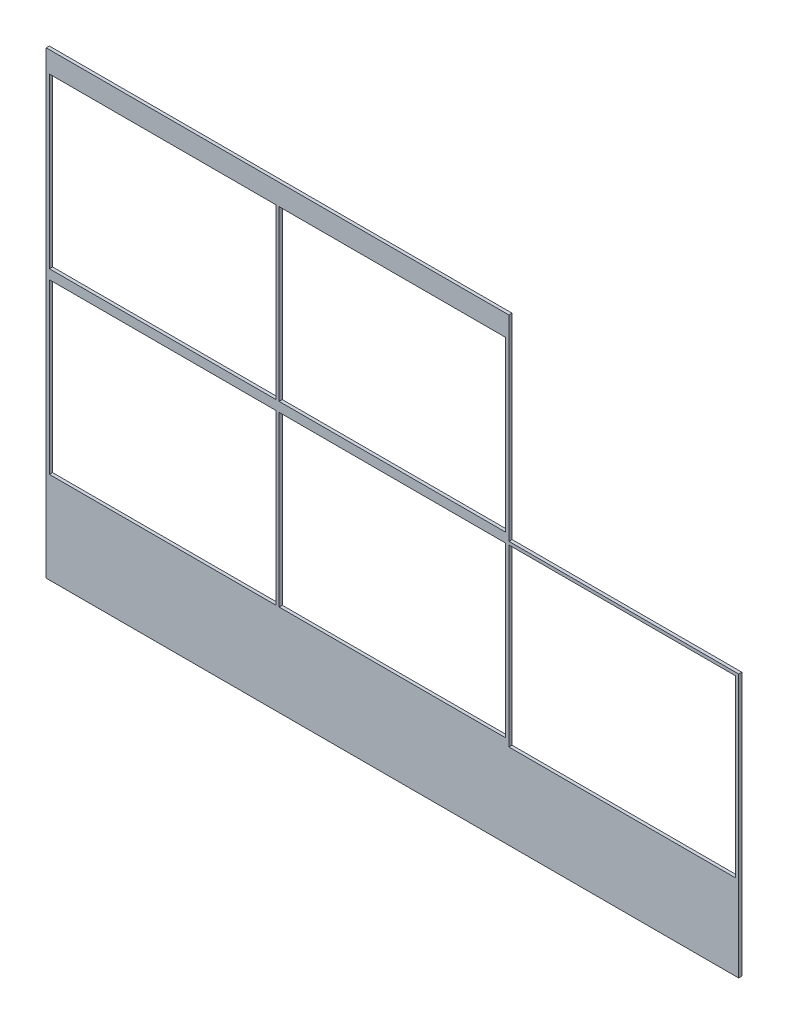
SolidWorks part; units mm, degrees
ref_plane "Спереди" through (0, 0, 0) normal (0, 0, 1) x (1, 0, 0)
ref_plane "Сверху" through (0, 0, 0) normal (0, 1, 0) x (1, 0, 0)
ref_plane "Справа" through (0, 0, 0) normal (1, 0, 0) x (0, 0, -1)
sketch "Эскиз1" plane through (0, 0, 0) normal (0, 0, 1) x (1, 0, 0)
  line L2 (-431, -435.8) -> (-431, 435.8)
  line L3 (-431, 435.8) -> (447, 435.8)
  line L4 (447, 63.8) -> (447, 435.8)
  line L6 (447, -429.8) -> (447, 435.8) construction
  line L8 (883, -435.8) -> (883, 63.8)
  line L9 (883, 63.8) -> (447, 63.8)
  line L11 (-431, -435.8) -> (883, -435.8)
  line L13 (-431, 63.8) -> (883, 63.8) construction
  line L14 (-431, -435.8) -> (883, -435.8) construction
  line L15 (-431, -435.8) -> (-431, 435.8) construction
  line L17 (-431, 435.8) -> (447, 435.8) construction
  point P13 (447, 63.8)
extrude "Бобышка-Вытянуть1" add sketch "Эскиз1" against normal blind 6
sketch "Эскиз2" plane through (0, 0, -6) normal (0, 0, -1) x (-1, 0, 0)
  line L1 (-11, 395.8) -> (-441, 395.8)
  line L2 (-11, 395.8) -> (-11, 75.8)
  line L3 (-11, 75.8) -> (-441, 75.8)
  line L4 (-441, 395.8) -> (-441, 75.8)
  line L10 (-447, 63.8) -> (-447, 435.8) construction
  line L11 (-943, 395.8) -> (441, 395.8) construction
  dimension "D2" = 320
  dimension "D1" = 430
  dimension "D3" = 6
extrude "Вырез-Вытянуть1" cut sketch "Эскиз2" against normal through all
pattern_linear "Линейный массив1" count 2 spacing 436 along (-1, 0, 0) count 2 spacing 338 along (0, -1, 0) of "Вырез-Вытянуть1"
sketch "Эскиз3" plane through (0, 0, 0) normal (0, 0, 1) x (1, 0, 0)
  line L0 (441, 57.8) -> (441, -262.2) construction
  line L1 (447, 57.8) -> (877, 57.8)
  line L2 (447, 57.8) -> (447, -274.2)
  line L3 (447, -274.2) -> (877, -274.2)
  line L4 (877, 57.8) -> (877, -274.2)
  line L5 (11, 57.8) -> (441, 57.8) construction
  dimension "D1" = 430
  dimension "D3" = 6
  dimension "D2" = 332
extrude "Вырез-Вытянуть2" cut sketch "Эскиз3" against normal through all
equation "\"Ширина груза\"= 420"
equation "\"Глубина груза\"= 490"
equation "\"Высота груза\"= 297"
equation "\"Ширина ячейки\"= \"Ширина груза\" + 10"
equation "\"Глубина ячейки\"= \"Глубина груза\" + 10"
equation "\"Высота ячейки\"= \"Высота груза\" + 10 + 13"
equation "\"Колво ячеек ширина\"= 2"
equation "\"Колво ячеек высота\"= 2"
equation "\"Толщина стенки\" = 6"
equation "\"Крепление дверцы\"= 5 "
equation "\"Ширина рейки\"= \"Толщина шестерни\""
equation "\"Высота рейки\"= 20"
equation "\"Высота пола\"= \"Толщина стенки\" * 2"
equation "\"Колво полозьев\"= 5"
equation "\"Отступ рейки\"= 20"
equation "\"Глубина каретки\"= \"Глубина ячейки\" + 30 + \"Мотор Y высота корпуса\" + 20"
equation "\"Длинна рейки\"= ( \"Ширина ячейки\" + \"Толщина стенки\" + \"Крепление дверцы\" ) * \"Колво ячеек ширина\" + \"Ширина ячейки выгрузки\" * \"Колво выгрузки\" + \"Толщина стенки\""
equation "\"Отступ шпильки\"= 26"
equation "\"Диаметр шпильки\"= 5"
equation "\"Длинна шпильки\"= ( \"Высота ячейки\" + \"Толщина стенки\" + \"Высота пола\" ) * \"Колво ячеек высота\" + ( \"Толщина стенки\" + \"Отступ рейки\" ) * 2 "
equation "\"Ширина пластины\"= 50  "
equation "\"Высота зона выгрузки\"= \"Высота ячейки\" * 2 + \"Толщина стенки\" * 2"
equation "\"Колво выгрузки\"= 1"
equation "\"Ширина ячейки выгрузки\"= \"Ширина ячейки\" + \"Толщина стенки\" + \"Отступ крепления мотора фиксации\"*2"
equation "\"Отступ крепления мотора фиксации\" = 30"
equation "\"Мотор X ширина корпуса\"= 42.3"
equation "\"Мотор X высота корпуса\"= 42.3"
equation "\"Мотор X длина корпуса\"= 40"
equation "\"Мотор X вылет вала\"= 19.8"
equation "\"Мотор Y ширина корпуса\"= 42.3"
equation "\"Мотор Y высота корпуса\"= 42.3"
equation "\"Мотор Y длина корпуса\"= 48"
equation "\"Мотор Y вылет вала\"= 30"
equation "\"Мотор Z ширина корпуса\"= 42"
equation "\"Мотор Z высота корпуса\"= 42"
equation "\"Мотор Z длина корпуса\"= 40"
equation "\"Мотор Z вылет вала\"= 23"
equation "\"Мотор диаметр вала ПРЕДВ\"= 5"
equation "\"Мотор шаг крепления ПРЕДВ\"= 31"
equation "\"Мотор диаметр отверстий ПРЕДВ\"= 3"
equation "\"Мотор глубина отверстий ПРЕДВ\"= 4.5"
equation "\"Мотор диаметр буртика ПРЕДВ\"= 22"
equation "\"Мотор высота буртика ПРЕДВ\"= 2"
equation "\"Мотор диаметр шкива ПРЕДВ\"= 16"
equation "\"Мотор длина шкива ПРЕДВ\"= 12"
equation "\"Мотор отступ шкива ПРЕДВ\"= 5"
equation "\"Мотор X шаг градусов\"= 1.8"
equation "\"Мотор Y шаг градусов\"= 1.8"
equation "\"Мотор Z шаг градусов\"= 1.8"
equation "\"Мотор Y диаметр ротора\"= 25.78"
equation "\"Толщина шестерни\"= 10"
equation "\"D1@Бобышка-Вытянуть1\"=\"Толщина стенки\""
equation "\"D1@Линейный массив1\"=\"Колво ячеек ширина\""
equation "\"D2@Линейный массив1\"=\"Колво ячеек высота\""
equation "\"D3@Линейный массив1\"=\"Ширина ячейки\"+\"Толщина стенки\""
equation "\"D4@Линейный массив1\"=\"Высота ячейки\" + \"Высота пола\"+\"Толщина стенки\""
equation "\"D1@Эскиз2\"=\"Ширина ячейки\""
equation "\"D3@Эскиз2\"=\"Толщина стенки\""
equation "\"D1@Эскиз3\"=\"Ширина ячейки\""
equation "\"D2@Эскиз3\"=\"Высота ячейки\" + \"Высота пола\""
equation "\"D3@Эскиз3\"=\"Толщина стенки\""
